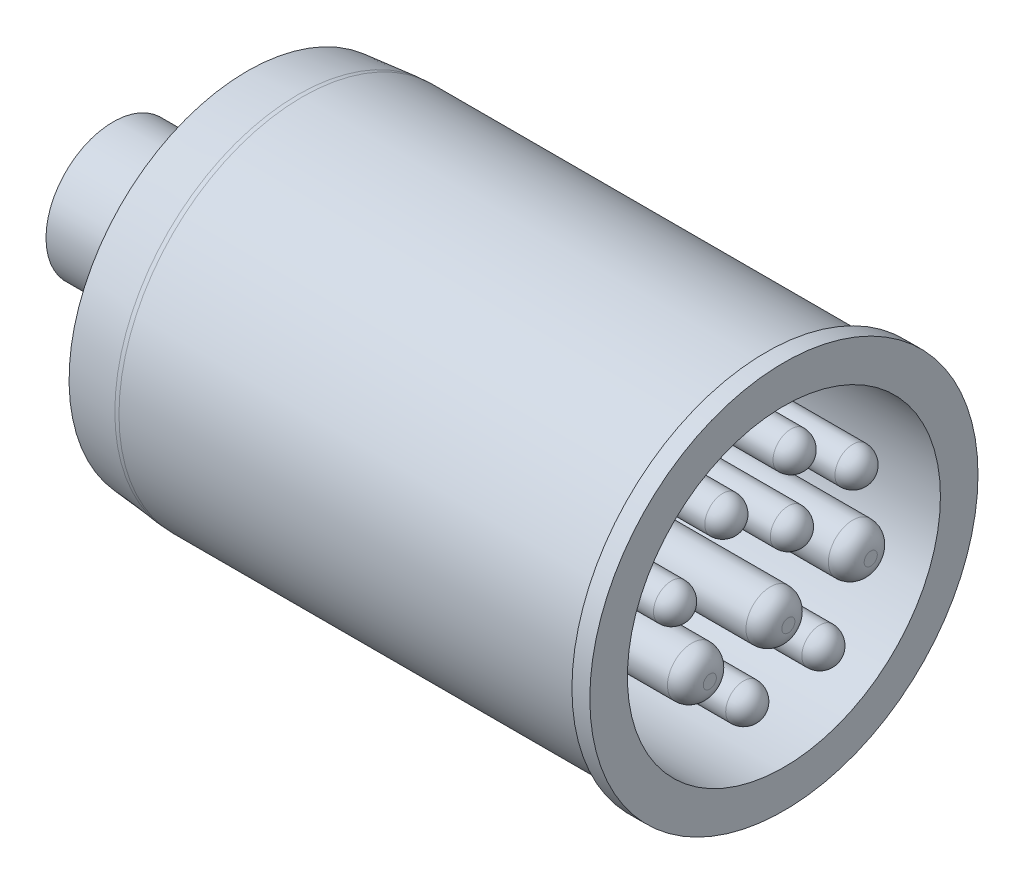
SolidWorks part; units mm, degrees
ref_plane "Front Plane" through (0, 0, 0) normal (0, 0, 1) x (1, 0, 0)
ref_plane "Top Plane" through (0, 0, 0) normal (0, 1, 0) x (1, 0, 0)
ref_plane "Right Plane" through (0, 0, 0) normal (1, 0, 0) x (0, 0, -1)
sketch "Sketch3" plane through (0, 0, 0) normal (0, 0, 1) x (1, 0, 0)
  line L0 (0, 0) -> (0, -50000) construction
  line L1 (0, 0) -> (50000, 0) construction
  line L2 (65, 0) -> (65, 20.5)
  line L3 (65, 17.5) -> (11.0609, 17.5) construction
  line L4 (11.0609, 17.5) -> (-6.8538, 15.75) construction
  line L5 (-6.8538, 15.75) -> (-25, 15.75) construction
  line L6 (-25, 15.75) -> (-25, 20.5) construction
  line L7 (-42, 0) -> (-42, 53.8042) construction
  line L8 (-25, 20.5) -> (-27.6909, 20.5) construction
  line L9 (-42, 10) -> (-43.4514, 10) construction
  line L10 (-42, 13) -> (-42, 0) construction
  line L11 (-42, 0) -> (65, 0)
  line L12 (65, 20.5) -> (10.9147, 20.5)
  line L13 (10.9147, 20.5) -> (-7, 18.75)
  line L14 (-7, 18.75) -> (-22, 18.75)
  line L15 (-22, 18.75) -> (-22, 23.5)
  line L16 (-22, 23.5) -> (-27.6909, 23.5)
  line L17 (-42, 13) -> (-45, 13)
  line L18 (-45, 13) -> (-45, 0)
  line L19 (-45, 0) -> (-42, 0)
  arc A0 (-42, 10) -> (-35.3224, 14.9) centre (-42, 17) ccw construction
  arc A1 (-35.3224, 14.9) -> (-27.6909, 20.5) centre (-27.6909, 12.5) cw construction
  arc A2 (-38.1842, 15.8) -> (-27.6909, 23.5) centre (-27.6909, 12.5) cw
  arc A3 (-42, 13) -> (-38.1842, 15.8) centre (-42, 17) ccw
  dimension "D8" = 20
  dimension "D9" = 7
  dimension "D10" = 8
  dimension "D1" = 17.5
  dimension "D2" = 23
  dimension "D3" = 18
  dimension "D4" = 15.75
  dimension "D5" = 41
  dimension "D6" = 110
  dimension "D7" = 3
  dimension "D11" = 3
  dimension "D12" = 45
  dimension "D13" = 15
revolve "Revolve1" add sketch "Sketch3" angle 360 about L1
fillet "Fillet1" radius 5 1 edges at (-22, 0, 18.75)
fillet "Fillet2" radius 0.3 1 edges at (-22, 0, 23.5)
fillet "Fillet3" radius 5 2 edges at (10.9147, 0, 20.5) (-7, 0, 18.75)
sketch "Sketch4" plane through (65, 0, 0) normal (1, 0, 0) x (0, 0, -1)
  circle A2 centre (0, 0) radius 17.5
  circle A3 centre (0, 0) radius 17.5
  dimension "D1" = 3
extrude "Cut-Extrude1" cut sketch "Sketch4" against normal blind 35
sketch "Sketch5" plane through (30, 0, 0) normal (1, 0, 0) x (0, 0, -1)
  line L0 (0, 0) -> (0, -50000) construction
  line L1 (0, 0) -> (50000, 0) construction
  circle A0 centre (2.4852, 3.5673) radius 2.0006
  circle A1 centre (2.7845, 10.8694) radius 2.0006
  circle A2 centre (-4.8439, 8.4442) radius 2.0006
  circle A3 centre (-10.5763, 2.8441) radius 2.0006
  circle A4 centre (9.7074, 5.9308) radius 2.0006
  circle A5 centre (-2.5069, -10.8694) radius 2.0006
  circle A6 centre (6.0034, -9.7229) radius 2.0006
  circle A7 centre (9.7074, -2.1386) radius 2.7332
  circle A8 centre (0.4915, -3.9906) radius 2.7332
  circle A9 centre (-8.2833, -5.0489) radius 2.7332
extrude "Boss-Extrude1" add sketch "Sketch5" along normal up to surface (35 mm away) up to face at (65, 0, -17.5)
fillet "Fillet4" radius 2 10 edges at (65, -10.8694, 4.5075) (65, -9.7229, -4.0028) (65, -2.1386, -6.9742) (65, -3.9906, 2.2416) (65, -5.0489, 11.0165) (65, 2.8441, 12.5769) (65, 3.5673, -0.4846) (65, 5.9308, -7.7068) (65, 10.8694, -0.7839) (65, 8.4442, 6.8446)
sketch "Sketch6" plane through (65, 0, 0) normal (1, 0, 0) x (0, 0, -1)
  circle A0 centre (0, 0) radius 20.5 construction
  circle A1 centre (0, 0) radius 20.5
  circle A2 centre (0, 0) radius 21.7
  dimension "D1" = 1.2
extrude "Boss-Extrude2" add sketch "Sketch6" against normal blind 2
sketch "Sketch7" plane through (-45, 0, 0) normal (-1, 0, 0) x (0, 0, 1)
  circle A0 centre (0, 0) radius 7.5
  dimension "D1" = 15
extrude "Extrude-Thin1" add sketch "Sketch7" along normal blind 15 thin thin type one direction reverse wall 0.5
sketch "Sketch8" plane through (0, 0, 0) normal (0, 0, 1) x (1, 0, 0)
  line L0 (-45, 13) -> (-45, -49987) construction
  line L2 (-45, 24.8581) -> (5, 24.8581)
  line L3 (-45, 24.8581) -> (-45, -25.1419)
  line L4 (-45, -25.1419) -> (5, -25.1419)
  line L5 (5, 24.8581) -> (5, -25.1419)
  dimension "D1" = 50
  dimension "D2" = 50
extrude "Cut-Extrude2" cut sketch "Sketch8" against normal through all both and the other way through all
move or copy body "Body-Move/Copy1" bodies to move or copy 108 copy no translate (-50, 0, 0)
